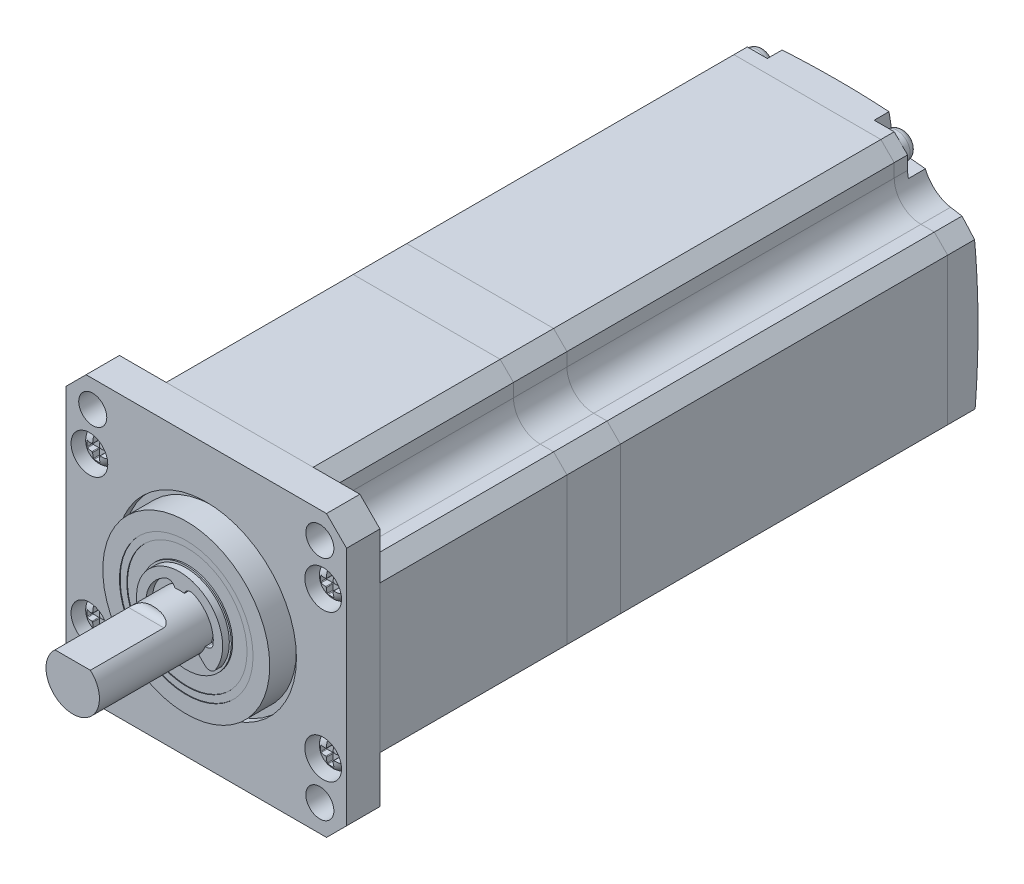
SolidWorks part; units mm, degrees
other "攝影機1"
other "標示1"
sketch "草圖18" plane through (42, 0, 25) normal (0.379, 0.6674, 0.641) x (0.8211, 0.0769, -0.5655)
other "標示2"
sketch "草圖19" plane through (42, -42, -90.0911) normal (0.5104, -0.715, -0.4778) x (-0.4504, 0.2511, -0.8568)
ref_plane "前基準面" through (0, 0, 0) normal (0, 0, 1) x (1, 0, 0)
ref_plane "上基準面" through (0, 0, 0) normal (0, 1, 0) x (1, 0, 0)
ref_plane "右基準面" through (0, 0, 0) normal (1, 0, 0) x (0, 0, -1)
sketch "草圖1" plane through (0, 0, 0) normal (0, 0, 1) x (1, 0, 0)
  line L0 (0, 0) -> (42, -42) construction
  line L1 (39, -42) -> (3, -42)
  line L2 (42, -39) -> (42, -3)
  line L3 (39, 0) -> (3, 0)
  line L4 (0, -39) -> (0, -3)
  line L5 (42, 0) -> (0, -42) construction
  line L6 (42, -3) -> (39, 0)
  line L7 (3, 0) -> (0, -3)
  line L8 (3, -42) -> (0, -39)
  line L9 (39, -42) -> (42, -39)
  circle A0 centre (4, -4) radius 2.1
  circle A1 centre (38, -4) radius 2.1
  circle A2 centre (4, -38) radius 2.1
  circle A3 centre (38, -38) radius 2.1
  point P0 (0, 0)
  dimension "D3" = 4.2
  dimension "D4" = 4.2
  dimension "D5" = 4.2
  dimension "D6" = 4.2
  dimension "D7" = 4
  dimension "D8" = 4
  dimension "D9" = 4
  dimension "D10" = 4
  dimension "D11" = 4
  dimension "D12" = 4
  dimension "D13" = 4
  dimension "D14" = 4
  dimension "D1" = 42
  dimension "D2" = 42
extrude "填料-伸長1" add sketch "草圖1" along normal blind 5
sketch "草圖2" plane through (0, 0, 5) normal (0, 0, 1) x (1, 0, 0)
  line L0 (1.5, -1.5) -> (40.5, -40.5) construction
  line L1 (3, 0) -> (0, -3) construction
  line L2 (39, -42) -> (42, -39) construction
  line L3 (40.5, -1.5) -> (1.5, -40.5) construction
  line L4 (42, -3) -> (39, 0) construction
  line L5 (0, -39) -> (3, -42) construction
  circle A0 centre (21, -21) radius 12.5
  circle A1 centre (21, -21) radius 13.5
  circle A2 centre (21, -21) radius 4
  dimension "D1" = 25
  dimension "D2" = 1
  dimension "D3" = 8
extrude "填料-伸長2" add sketch "草圖2" along normal blind 3 contours A0 A2 | A2 region at (8.8536, -21, 5) region at (21, -21, 5)
extrude "填料-伸長3" add sketch "草圖2<3>" along normal blind 20 contours A2
sketch "草圖2<3>" plane through (0, 0, 5) normal (0, 0, 1) x (1, 0, 0) same geometry as "草圖2"
extrude "除料-伸長1" cut sketch "草圖2<4>" against normal blind 1 contours A1 A0 region at (7.8818, -21, 5)
sketch "草圖2<4>" plane through (0, 0, 5) normal (0, 0, 1) x (1, 0, 0) same geometry as "草圖2"
sketch "草圖3" plane through (0, 0, 25) normal (0, 0, 1) x (1, 0, 0)
  line L0 (18.3542, -18) -> (23.6458, -18)
  circle A0 centre (21, -21) radius 4
  point P5 (21, -18)
  circle M3 centre (21, -21) radius 4
  dimension "D1" = 8
  dimension "D2" = 3
extrude "除料-伸長2" cut sketch "草圖3" against normal blind 12 contours L0 M3 region at (21, -17.5954, 25)
fillet "圓角1" radius 1 1 edges at (21, -18, 13)
sketch "草圖5" plane through (0, 0, 8) normal (0, 0, 1) x (1, 0, 0)
  circle A0 centre (21, -21) radius 6.75
  circle A1 centre (21, -21) radius 10
  circle A2 centre (21, -21) radius 12.5 construction
  circle A3 centre (21, -21) radius 9
  dimension "D1" = 13.5
  dimension "D2" = 2.5
  dimension "D3" = 1
extrude "除料-伸長3" cut sketch "草圖5" against normal blind 0.1 contours A1 A3 region at (11.2828, -21, 8)
extrude "除料-伸長4" cut sketch "草圖5<4>" against normal blind 0.2 contours A3 A0 region at (12.2546, -21, 8)
sketch "草圖5<4>" plane through (0, 0, 8) normal (0, 0, 1) x (1, 0, 0) same geometry as "草圖5"
sketch "草圖6" plane through (0, 0, 0) normal (0, 0, -1) x (-1, 0, 0)
  line L0 (-39, 0) -> (-3, 0) construction
  line L1 (-34, -2) -> (-32, 0)
  line L2 (-8, -2) -> (-10, 0)
  line L6 (0, -32) -> (0, -10)
  line L7 (0, -3) -> (0, -39) construction
  line L8 (-2, -8) -> (0, -10)
  line L9 (-2, -34) -> (0, -32)
  line L10 (-38, -34) -> (-40, -34)
  line L11 (-34, -38) -> (-34, -40)
  line L12 (-34, -4) -> (-34, -2)
  line L13 (-38, -8) -> (-40, -8)
  line L14 (-8, -4) -> (-8, -2)
  line L15 (-4, -8) -> (-2, -8)
  line L16 (-4, -34) -> (-2, -34)
  line L17 (-8, -38) -> (-8, -40)
  line L18 (-32, 0) -> (-10, 0)
  line L19 (-42, -32) -> (-42, -10)
  line L20 (-32, -42) -> (-10, -42)
  line L21 (-8, -40) -> (-10, -42)
  line L22 (-34, -40) -> (-32, -42)
  line L23 (-40, -34) -> (-42, -32)
  line L24 (-40, -8) -> (-42, -10)
  arc A0 (-4, -34) -> (-8, -38) centre (-4, -38) ccw
  arc A4 (-8, -4) -> (-4, -8) centre (-4, -4) ccw
  arc A5 (-38, -8) -> (-34, -4) centre (-38, -4) ccw
  arc A6 (-34, -38) -> (-38, -34) centre (-38, -38) ccw
  point P7 (-21, -21)
  point P26 (-42, -34)
  point P28 (-34, -42)
  point P30 (-34, 0)
  point P32 (-42, -8)
  point P34 (-8, 0)
  point P36 (0, -8)
  point P38 (0, -34)
  point P40 (-8, -42)
  dimension "D1" = 42
  dimension "D2" = 42
extrude "填料-伸長4" add sketch "草圖6" along normal blind 90
sketch "草圖7" plane through (0, 0, 8) normal (0, 0, 1) x (1, 0, 0)
  line L0 (21, -21) -> (21, -27.45) construction
  line L1 (16.4392, -25.5608) -> (18.1362, -23.8638)
  line L2 (23.8638, -23.8638) -> (25.5608, -25.5608)
  line L3 (16.1265, -22.3236) -> (17.1724, -22.3236)
  line L4 (25.8725, -22.3271) -> (24.8264, -22.3271)
  line L5 (20.1231, -16.0267) -> (20.2967, -17.0115)
  line L6 (21.8769, -16.0267) -> (21.7033, -17.0115)
  line L7 (21, -21) -> (21, -14.55) construction
  arc A0 (25.5608, -25.5608) -> (16.4392, -25.5608) centre (21, -21) ccw
  arc A1 (23.8638, -23.8638) -> (24.8264, -22.3271) centre (21, -21) ccw
  arc A2 (25.8725, -22.3271) -> (21.8769, -16.0267) centre (21, -21) ccw
  arc A3 (20.1231, -16.0267) -> (16.1265, -22.3236) centre (21, -21) ccw
  arc A4 (21.7033, -17.0115) -> (20.2967, -17.0115) centre (21, -21) ccw
  arc A5 (17.1724, -22.3236) -> (18.1362, -23.8638) centre (21, -21) ccw
  dimension "D1" = 12.9
  dimension "D2" = 8.1
  dimension "D5" = 1
  dimension "D3" = 45
  dimension "D4" = 45
  dimension "D6" = 10
  dimension "D7" = 10
extrude "填料-伸長5" add sketch "草圖7" along normal blind 1
fillet "圓角2" radius 1 6 edges at (20.1231, -16.0267, 8.5) (21.8769, -16.0267, 8.5) (25.8725, -22.3271, 8.5) (16.1265, -22.3236, 8.5) (25.5608, -25.5608, 8.5) (16.4392, -25.5608, 8.5)
sketch "草圖8" plane through (0, 0, 5) normal (0, 0, 1) x (1, 0, 0)
  line L0 (0, -3) -> (0, -39) construction
  line L1 (42, -39) -> (42, -3) construction
  circle A0 centre (3.5, -10) radius 2.75
  circle A1 centre (38.5, -10) radius 2.75
  circle A2 centre (3.5, -32) radius 2.75
  circle A3 centre (38.5, -32) radius 2.75
  circle A4 centre (38, -38) radius 2.1 construction
  circle A5 centre (38, -4) radius 2.1 construction
  circle A6 centre (4, -4) radius 2.1 construction
  circle A7 centre (4, -38) radius 2.1 construction
  dimension "D1" = 5.5
  dimension "D2" = 5.5
  dimension "D3" = 5.5
  dimension "D4" = 5.5
  dimension "D5" = 3.5
  dimension "D6" = 3.5
  dimension "D7" = 3.5
  dimension "D8" = 3.5
  dimension "D9" = 6
  dimension "D10" = 6
  dimension "D11" = 6
  dimension "D12" = 6
extrude "除料-伸長5" cut sketch "草圖8" against normal blind 3
sketch "草圖9" plane through (0, 0, 2) normal (0, 0, 1) x (1, 0, 0)
  line L0 (0, -21) -> (42, -21) construction
  line L1 (0, -3) -> (0, -39) construction
  line L2 (42, -39) -> (42, -3) construction
  line L3 (21, 0) -> (21, -42) construction
  line L4 (39, 0) -> (3, 0) construction
  line L5 (3, -42) -> (39, -42) construction
  circle A0 centre (3.5, -10) radius 2.5
  circle A1 centre (38.5, -10) radius 2.5
  circle A2 centre (38.5, -32) radius 2.5
  circle A3 centre (3.5, -32) radius 2.5
  dimension "D1" = 5
extrude "填料-伸長6" add sketch "草圖9" along normal blind 2
sketch "草圖10" plane through (0, 0, 4) normal (0, 0, 1) x (1, 0, 0)
  line L0 (0, -21) -> (42, -21) construction
  line L1 (2, -10.5) -> (3, -10.5)
  line L2 (2, -10.5) -> (2, -9.5)
  line L3 (2, -9.5) -> (3, -9.5)
  line L4 (5, -10.5) -> (5, -9.5)
  line L5 (0, -3) -> (0, -39) construction
  line L6 (42, -39) -> (42, -3) construction
  line L7 (4, -11.5) -> (3, -11.5)
  line L8 (4, -11.5) -> (4, -10.5)
  line L9 (4, -8.5) -> (3, -8.5)
  line L10 (3, -11.5) -> (3, -10.5)
  line L11 (21, 0) -> (21, -42) construction
  line L12 (39, 0) -> (3, 0) construction
  line L13 (3, -9.5) -> (3, -8.5)
  line L14 (3, -42) -> (39, -42) construction
  line L15 (4, -9.5) -> (5, -9.5)
  line L16 (4, -9.5) -> (4, -8.5)
  line L17 (4, -10.5) -> (5, -10.5)
  line L18 (38, -9.5) -> (37, -9.5)
  line L19 (37, -10.5) -> (37, -9.5)
  line L20 (38, -10.5) -> (37, -10.5)
  line L21 (38, -11.5) -> (38, -10.5)
  line L22 (38, -11.5) -> (39, -11.5)
  line L23 (39, -11.5) -> (39, -10.5)
  line L24 (40, -10.5) -> (39, -10.5)
  line L25 (40, -10.5) -> (40, -9.5)
  line L26 (40, -9.5) -> (39, -9.5)
  line L27 (39, -9.5) -> (39, -8.5)
  line L28 (38, -8.5) -> (39, -8.5)
  line L29 (38, -9.5) -> (38, -8.5)
  line L30 (38, -32.5) -> (38, -33.5)
  line L31 (38, -33.5) -> (39, -33.5)
  line L32 (39, -32.5) -> (39, -33.5)
  line L33 (40, -32.5) -> (39, -32.5)
  line L34 (40, -31.5) -> (40, -32.5)
  line L35 (40, -31.5) -> (39, -31.5)
  line L36 (39, -30.5) -> (39, -31.5)
  line L37 (38, -30.5) -> (39, -30.5)
  line L38 (38, -30.5) -> (38, -31.5)
  line L39 (38, -31.5) -> (37, -31.5)
  line L40 (37, -31.5) -> (37, -32.5)
  line L41 (38, -32.5) -> (37, -32.5)
  line L42 (4, -32.5) -> (5, -32.5)
  line L43 (5, -31.5) -> (5, -32.5)
  line L44 (4, -31.5) -> (5, -31.5)
  line L45 (4, -30.5) -> (4, -31.5)
  line L46 (4, -30.5) -> (3, -30.5)
  line L47 (3, -30.5) -> (3, -31.5)
  line L48 (2, -31.5) -> (3, -31.5)
  line L49 (2, -31.5) -> (2, -32.5)
  line L50 (2, -32.5) -> (3, -32.5)
  line L51 (3, -32.5) -> (3, -33.5)
  line L52 (4, -33.5) -> (3, -33.5)
  line L53 (4, -32.5) -> (4, -33.5)
  circle A0 centre (3.5, -10) radius 2.5 construction
  point P0 (3.5, -10)
  point P6 (3.5, -10)
  point P16 (3.5, -8.5)
  point P17 (3.5, -11.5)
  point P19 (2, -10)
  point P20 (5, -10)
  dimension "D1" = 1.5
  dimension "D2" = 1.5
  dimension "D3" = 1.5
  dimension "D4" = 1.5
  dimension "D5" = 1
  dimension "D6" = 1
extrude "除料-伸長6" cut sketch "草圖10" against normal blind 1
fillet "圓角3" radius 1.6 4 edges at (6, -10, 4) (41, -32, 4) (1, -32, 4) (36, -10, 4)
fillet "圓角4" radius 0.1 48 edges at (3, -11.5, 3.4239) (4, -11.5, 3.4239) (3, -10.5, 3.5) (2, -10.5, 3.4239) (2, -9.5, 3.4239) (3, -9.5, 3.5) (4, -10.5, 3.5) (5, -10.5, 3.4239) (5, -9.5, 3.4239) (4, -9.5, 3.5) (4, -8.5, 3.4239) (3, -8.5, 3.4239) (40, -32.5, 3.4239) (40, -31.5, 3.4239) (39, -31.5, 3.5) (39, -30.5, 3.4239) (38, -30.5, 3.4239) (38, -31.5, 3.5) (37, -31.5, 3.4239) (37, -32.5, 3.4239) (38, -32.5, 3.5) (38, -33.5, 3.4239) (39, -33.5, 3.4239) (39, -32.5, 3.5) (39, -11.5, 3.4239) (38, -11.5, 3.4239) (39, -10.5, 3.5) (40, -10.5, 3.4239) (40, -9.5, 3.4239) (39, -9.5, 3.5) (39, -8.5, 3.4239) (38, -8.5, 3.4239) (38, -9.5, 3.5) (37, -9.5, 3.4239) (37, -10.5, 3.4239) (38, -10.5, 3.5) (4, -33.5, 3.4239) (3, -33.5, 3.4239) (2, -32.5, 3.4239) (3, -32.5, 3.5) (4, -32.5, 3.5) (5, -32.5, 3.4239) (5, -31.5, 3.4239) (4, -31.5, 3.5) (4, -30.5, 3.4239) (3, -30.5, 3.4239) (3, -31.5, 3.5) (2, -31.5, 3.4239)
sketch "草圖11" plane through (0, 0, -90) normal (0, 0, -1) x (-1, 0, 0)
  line L1 (-10, 0) -> (-32, 0) construction
  line L2 (-32, -42) -> (-10, -42) construction
  line L6 (-34, -38) -> (-34, -40) construction
  line L7 (-34, -2) -> (-34, -4) construction
  line L8 (-8, -4) -> (-8, -2) construction
  line L9 (-8, -40) -> (-8, -38) construction
  line L10 (-29, -2.5) -> (-29, 0)
  line L11 (-31.5, -5) -> (-34.127, -5)
  line L12 (-10.5, -5) -> (-7.873, -5)
  line L13 (-13, -2.5) -> (-13, 0)
  line L14 (-10.5, -37) -> (-7.873, -37)
  line L15 (-13, -39.5) -> (-13, -42)
  line L16 (-31.5, -37) -> (-34.127, -37)
  line L17 (-29, -39.5) -> (-29, -42)
  line L18 (-34.127, -37) -> (-34, -38)
  line L19 (-34, -38) -> (-34, -40)
  line L20 (-34, -40) -> (-32, -42)
  line L21 (-32, -42) -> (-29, -42)
  line L22 (-13, -42) -> (-10, -42)
  line L23 (-10, -42) -> (-8, -40)
  line L24 (-8, -40) -> (-8, -38)
  line L25 (-8, -38) -> (-7.873, -37)
  line L26 (-7.873, -5) -> (-8, -4)
  line L27 (-8, -4) -> (-8, -2)
  line L28 (-8, -2) -> (-10, 0)
  line L29 (-10, 0) -> (-13, 0)
  line L30 (-34.127, -5) -> (-34, -4)
  line L32 (-34, -2) -> (-32, 0)
  line L33 (-32, 0) -> (-29, 0)
  line L34 (-34, -2) -> (-34, -4)
  arc A1 (-31.5, -5) -> (-29, -2.5) centre (-31.5, -2.5) ccw
  arc A2 (-13, -2.5) -> (-10.5, -5) centre (-10.5, -2.5) ccw
  arc A3 (-29, -39.5) -> (-31.5, -37) centre (-31.5, -39.5) ccw
  arc A4 (-10.5, -37) -> (-13, -39.5) centre (-10.5, -39.5) ccw
  arc A5 (-38, -8) -> (-34, -4) centre (-38, -4) ccw construction
  arc A6 (-34, -38) -> (-38, -34) centre (-38, -38) ccw construction
  arc A7 (-34, -38) -> (-38, -34) centre (-38, -38) ccw construction
  arc A8 (-4, -34) -> (-8, -38) centre (-4, -38) ccw construction
  arc A9 (-38, -8) -> (-34, -4) centre (-38, -4) ccw construction
  arc A10 (-4, -34) -> (-8, -38) centre (-4, -38) ccw construction
  dimension "D2" = 5
  dimension "D3" = 5
  dimension "D4" = 5
  dimension "D5" = 5
extrude "除料-伸長7" cut sketch "草圖11" against normal blind 3 contours L34 L30 L11 A1 L10 L33 L32 | L29 L13 A2 L12 L26 L27 L28 | L25 L14 A4 L15 L22 L23 L24 | L21 L17 A3 L16 L18 L19 L20
ref_plane "平面2" through (21, 0, 0) normal (1, 0, 0) x (0, 0, -1)
sketch "草圖13" plane through (21, 0, 0) normal (1, 0, 0) x (0, 0, -1)
  line L0 (93.4025, -21.4865) -> (81.5023, -21.4865) construction
  line L2 (90.4615, -7.2042) -> (90.4615, 3.8549)
  line L3 (90.4615, 3.8549) -> (88.758, 3.8549)
  line L4 (90.4615, -7.2042) -> (90.4615, -0.4465) construction
  arc A0 (90.4615, -7.2042) -> (88.758, 3.8549) centre (-39.0133, -21.4865) ccw
revolve "除料-旋轉2" cut sketch "草圖13" angle 360 about L0
sketch "草圖16" plane through (0, 0, -87) normal (0, 0, -1) x (-1, 0, 0)
  line L0 (-31.5, -2.5) -> (-10.5, -2.5) construction
  line L1 (-10.5, -2.5) -> (-10.5, -39.5) construction
  line L2 (-10.5, -39.5) -> (-31.5, -39.5) construction
  line L3 (-31.5, -39.5) -> (-31.5, -2.5) construction
  line L4 (-21, -2.5) -> (-21, -39.5) construction
  line L5 (-31.5, -21) -> (-10.5, -21) construction
  circle A0 centre (-31.5, -2.5) radius 2
  circle A1 centre (-10.5, -2.5) radius 2
  circle A2 centre (-10.5, -39.5) radius 2
  circle A3 centre (-31.5, -39.5) radius 2
  dimension "D1" = 4
extrude "填料-伸長7" add sketch "草圖16" along normal blind 2
sketch "草圖17" plane through (0, 0, -89) normal (0, 0, -1) x (-1, 0, 0)
  line L0 (-31.5, -0.5) -> (-31.5, -4.5) construction
  line L1 (-33.0019, -2.9623) -> (-32.0019, -2.9623)
  line L2 (-33.0019, -2.9623) -> (-33.0019, -1.9623)
  line L3 (-33.0019, -1.9623) -> (-32.0019, -1.9623)
  line L4 (-30.0019, -2.9623) -> (-30.0019, -1.9623)
  line L5 (-31.0019, -3.9623) -> (-32.0019, -3.9623)
  line L6 (-31.0019, -3.9623) -> (-31.0019, -2.9623)
  line L7 (-31.0019, -0.9623) -> (-32.0019, -0.9623)
  line L8 (-32.0019, -3.9623) -> (-32.0019, -2.9623)
  line L9 (-32.0019, -1.9623) -> (-32.0019, -0.9623)
  line L10 (-31.0019, -1.9623) -> (-30.0019, -1.9623)
  line L11 (-31.0019, -1.9623) -> (-31.0019, -0.9623)
  line L12 (-31.0019, -2.9623) -> (-30.0019, -2.9623)
  line L13 (-31.5, -2.5) -> (-10.5, -2.5) construction
  line L14 (-10.5, -2.5) -> (-10.5, -39.5) construction
  line L15 (-10.5, -39.5) -> (-31.5, -39.5) construction
  line L16 (-31.5, -39.5) -> (-31.5, -2.5) construction
  line L17 (-21, -2.5) -> (-21, -39.5) construction
  line L18 (-31.5, -21) -> (-10.5, -21) construction
  line L19 (-8.9981, -2.9623) -> (-8.9981, -1.9623)
  line L20 (-8.9981, -1.9623) -> (-9.9981, -1.9623)
  line L21 (-9.9981, -1.9623) -> (-9.9981, -0.9623)
  line L22 (-10.9981, -0.9623) -> (-9.9981, -0.9623)
  line L23 (-10.9981, -1.9623) -> (-10.9981, -0.9623)
  line L24 (-10.9981, -1.9623) -> (-11.9981, -1.9623)
  line L25 (-11.9981, -2.9623) -> (-11.9981, -1.9623)
  line L26 (-10.9981, -2.9623) -> (-11.9981, -2.9623)
  line L27 (-10.9981, -3.9623) -> (-10.9981, -2.9623)
  line L28 (-10.9981, -3.9623) -> (-9.9981, -3.9623)
  line L29 (-9.9981, -3.9623) -> (-9.9981, -2.9623)
  line L30 (-8.9981, -2.9623) -> (-9.9981, -2.9623)
  line L31 (-8.9981, -39.0377) -> (-9.9981, -39.0377)
  line L32 (-9.9981, -38.0377) -> (-9.9981, -39.0377)
  line L33 (-10.9981, -38.0377) -> (-9.9981, -38.0377)
  line L34 (-10.9981, -38.0377) -> (-10.9981, -39.0377)
  line L35 (-10.9981, -39.0377) -> (-11.9981, -39.0377)
  line L36 (-11.9981, -39.0377) -> (-11.9981, -40.0377)
  line L37 (-10.9981, -40.0377) -> (-11.9981, -40.0377)
  line L38 (-10.9981, -40.0377) -> (-10.9981, -41.0377)
  line L39 (-10.9981, -41.0377) -> (-9.9981, -41.0377)
  line L40 (-9.9981, -40.0377) -> (-9.9981, -41.0377)
  line L41 (-8.9981, -40.0377) -> (-9.9981, -40.0377)
  line L42 (-8.9981, -39.0377) -> (-8.9981, -40.0377)
  line L43 (-33.0019, -39.0377) -> (-33.0019, -40.0377)
  line L44 (-33.0019, -40.0377) -> (-32.0019, -40.0377)
  line L45 (-32.0019, -40.0377) -> (-32.0019, -41.0377)
  line L46 (-31.0019, -41.0377) -> (-32.0019, -41.0377)
  line L47 (-31.0019, -40.0377) -> (-31.0019, -41.0377)
  line L48 (-31.0019, -40.0377) -> (-30.0019, -40.0377)
  line L49 (-30.0019, -39.0377) -> (-30.0019, -40.0377)
  line L50 (-31.0019, -39.0377) -> (-30.0019, -39.0377)
  line L51 (-31.0019, -38.0377) -> (-31.0019, -39.0377)
  line L52 (-31.0019, -38.0377) -> (-32.0019, -38.0377)
  line L53 (-32.0019, -38.0377) -> (-32.0019, -39.0377)
  line L54 (-33.0019, -39.0377) -> (-32.0019, -39.0377)
  circle A0 centre (-31.5, -2.5) radius 2 construction
  circle A1 centre (-31.5, -2.5) radius 2 construction
  point P7 (-31.5019, -2.4623)
  point P12 (-31.5019, -2.4623)
  point P20 (-31.5019, -0.9623)
  point P21 (-31.5019, -3.9623)
  point P23 (-33.0019, -2.4623)
  point P24 (-30.0019, -2.4623)
extrude "除料-伸長8" cut sketch "草圖17" against normal blind 1
fillet "圓角5" radius 1.1 4 edges at (33.5, -39.5, -89) (8.5, -39.5, -89) (29.5, -2.5, -89) (12.5, -2.5, -89)
ref_plane "平面3" through (0, 0, 0) normal (0, 0, -1) x (-1, 0, 0)
split "分割3" trim tools "平面3" bodies to split 118 resulting bodies 121 122
ref_plane "平面4" through (0, 0, -28) normal (0, 0, -1) x (-1, 0, 0)
split "分割4" trim tools "平面4" bodies to split 121 resulting bodies 123 124
ref_plane "平面5" through (0, 0, -36) normal (0, 0, -1) x (-1, 0, 0)
split "分割5" trim tools "平面5" bodies to split 123 resulting bodies 125 126
ref_plane "平面6" through (0, 0, -85) normal (0, 0, -1) x (-1, 0, 0)
split "分割6" trim tools "平面6" bodies to split 125 resulting bodies 127 128
equation "\"ˋ\"=0.152253"
